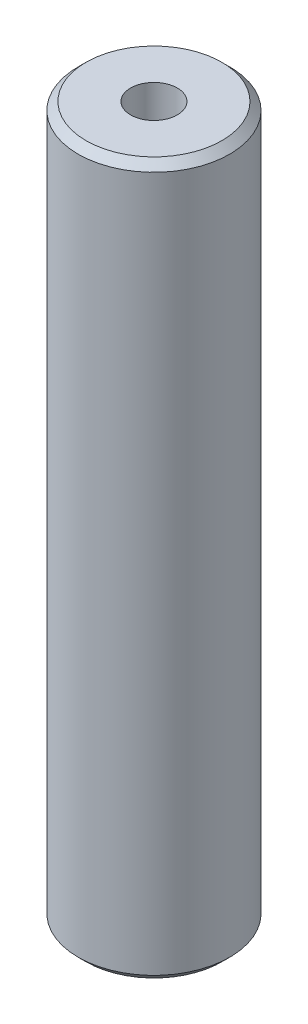
SolidWorks part; units mm, degrees
ref_plane "Front Plane" through (0, 0, 0) normal (0, 0, 1) x (1, 0, 0)
ref_plane "Top Plane" through (0, 0, 0) normal (0, 1, 0) x (1, 0, 0)
ref_plane "Right Plane" through (0, 0, 0) normal (1, 0, 0) x (0, 0, -1)
sketch "Sketch1" plane through (0, 0, 0) normal (0, 1, 0) x (1, 0, 0)
  circle A0 centre (0, 0) radius 45
  dimension "SHAFT_OD" = 90
extrude "Boss-Extrude1" add sketch "Sketch1" along normal blind 422.4703
sketch "Sketch2" plane through (0, 0, 0) normal (0, 1, 0) x (1, 0, 0)
  circle A0 centre (0, 0) radius 13.8739
  dimension "BORE_D" = 27.7478
extrude "Cut-Extrude1" cut sketch "Sketch2" along normal through all
chamfer "Chamfer1" distance 4.6446 angle 45 2 edges at (0, 422.4703, 45) (0, 0, 45)
